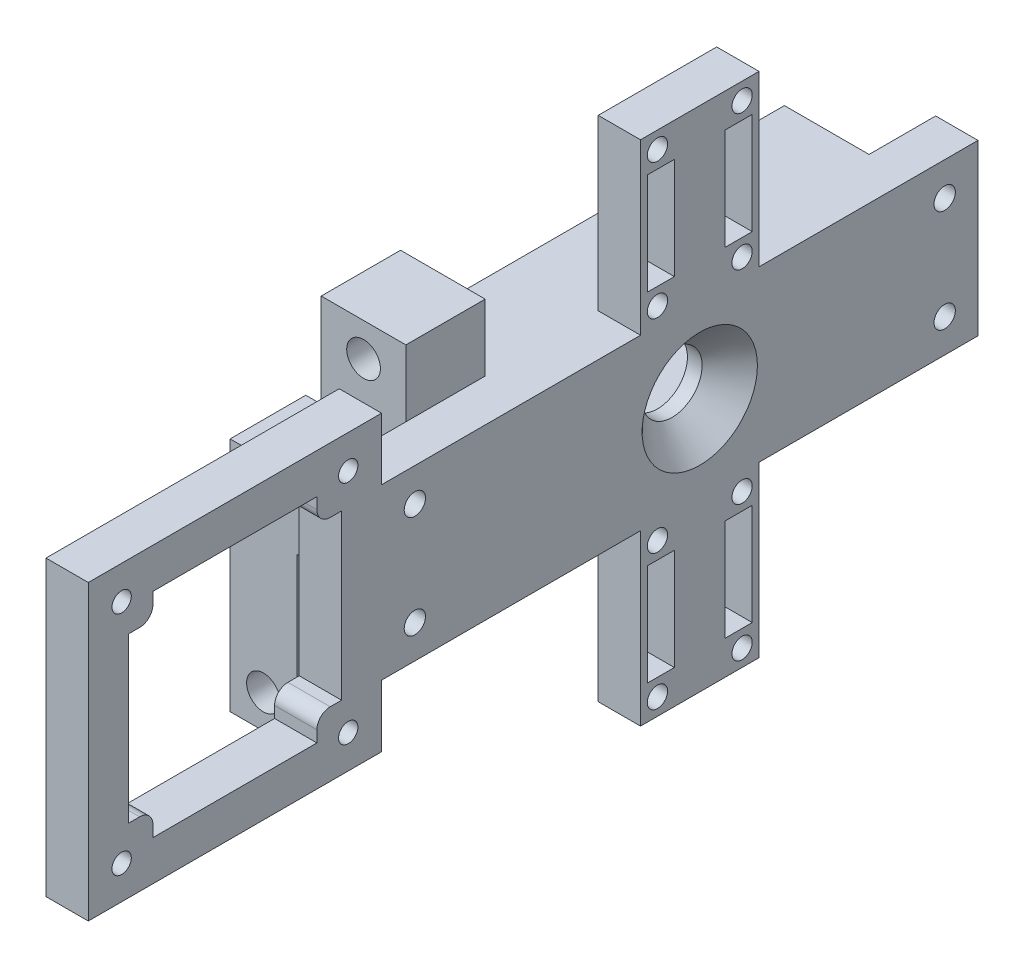
SolidWorks part; units mm, degrees
ref_plane "Front Plane" through (0, 0, 0) normal (0, 0, 1) x (1, 0, 0)
ref_plane "Top Plane" through (0, 0, 0) normal (0, 1, 0) x (1, 0, 0)
ref_plane "Right Plane" through (0, 0, 0) normal (1, 0, 0) x (0, 0, -1)
sketch "Sketch1" plane through (0, 0, 0) normal (0, 1, 0) x (1, 0, 0)
  line L1 (0, 0) -> (6.35, 0)
  line L2 (0, 0) -> (0, 89.5)
  line L3 (0, 89.5) -> (6.35, 89.5)
  line L4 (6.35, 0) -> (6.35, 89.5)
  dimension "D1" = 89.5
  dimension "D2" = 6.35
extrude "Boss-Extrude1" add sketch "Sketch1" along normal blind 25.4
sketch "Sketch2" plane through (0, 0, 0) normal (-1, 0, 0) x (0, 0, 1)
  line L0 (-89.5, 25.4) -> (0, 25.4) construction
  line L1 (-74.15, 20.05) -> (-21.35, 20.05)
  line L2 (-74.15, 20.05) -> (-74.15, 5.35)
  line L3 (-74.15, 5.35) -> (-21.35, 5.35)
  line L4 (-21.35, 20.05) -> (-21.35, 5.35)
  line L6 (-89.5, 25.4) -> (-89.5, 0) construction
  line L13 (-89.5, 0) -> (0, 0) construction
  line L14 (-79.5, 25.4) -> (-10, 25.4)
  line L15 (-79.5, 25.4) -> (-79.5, 0)
  line L16 (-79.5, 0) -> (-10, 0)
  line L17 (-10, 25.4) -> (-10, 0)
  line L18 (0, 25.4) -> (0, 0) construction
  dimension "D1" = 52.8
  dimension "D2" = 14.7
  dimension "D3" = 5.35
  dimension "D4" = 15.35
  dimension "D5" = 10
  dimension "D6" = 10
sketch "Sketch4" plane through (6.35, 0, 0) normal (1, 0, 0) x (0, 0, -1)
  line L0 (0, 25.4) -> (0, 0) construction
  line L1 (0, 34.7) -> (-44, 34.7)
  line L2 (0, 34.7) -> (0, -9.3)
  line L3 (0, -9.3) -> (-44, -9.3)
  line L4 (-44, 34.7) -> (-44, -9.3)
  line L6 (0, 25.4) -> (89.5, 25.4) construction
  circle A0 centre (-39, 29.7) radius 1.45
  circle A1 centre (-5, 29.7) radius 1.45
  circle A2 centre (-39, -4.3) radius 1.45
  circle A3 centre (-5, -4.3) radius 1.45
  dimension "D4" = 34
  dimension "D6" = 2.9
  dimension "D7" = 34
  dimension "D1" = 44
  dimension "D2" = 9.3
  dimension "D3" = 44
  dimension "D5" = 5
  dimension "D8" = 5
extrude "Boss-Extrude2" add sketch "Sketch4" against normal up to surface (6.35 mm away) up to face at (0, 12.7, -44.75)
hole_wizard "CSK for M8 Flat Head Machine Screw1" positions "Sketch6" profile "Sketch7" countersink size "M8" standard "ANSI Metric"
sketch "Sketch6" plane through (6.35, 0, 0) normal (1, 0, 0) x (0, 0, -1)
  line L1 (89.5, 25.4) -> (89.5, 0) construction
  line L2 (0, 25.4) -> (89.5, 25.4) construction
  point P0 (47.75, 12.7)
  dimension "D1" = 41.75
  dimension "D2" = 12.7
sketch "Sketch7" plane through (6.35, 12.7, -47.75) normal (0, 1, 0) x (0, 0, -1)
  line L0 (0, 0) -> (0, 20.2039)
  line L1 (0, 20.2039) -> (4.5, 17.5)
  line L2 (4.5, 17.5) -> (4.5, 4.15)
  line L3 (4.5, 4.15) -> (8.65, 0)
  line L5 (8.65, 0) -> (0, 0)
  line L6 (-4.5, 4.15) -> (-8.65, 0) construction
  line L10 (0, 20.2039) -> (-4.5, 17.5) construction
  line L11 (0, -6.35) -> (0, 107.95) construction
  dimension "Hole Dia." = 9
  dimension "Hole Depth" = 17.5
  dimension "Near C'Sink Dia." = 17.3
  dimension "Near C'Sink Angle" = 90
  dimension "Drill Angle" = 118
extrude "Boss-Extrude3" add sketch "Sketch2" along normal blind 12.7
sketch "Sketch9" plane through (0, 0, 0) normal (-1, 0, 0) x (0, 0, 1)
  line L1 (0, 34.7) -> (0, 25.4) construction
  line L2 (-10, 25.4) -> (0, 25.4) construction
  line L3 (-10, 0) -> (0, 0) construction
  line L4 (-89.5, 25.4) -> (-89.5, 0) construction
  circle A0 centre (-5, 20.4) radius 1.6
  circle A1 centre (-5, 5) radius 1.6
  circle A3 centre (-84.5, 5) radius 1.6
  circle A4 centre (-84.5, 20.4) radius 1.6
  dimension "D1" = 3.2
  dimension "D2" = 5
  dimension "D3" = 5
  dimension "D4" = 5
  dimension "D5" = 5
extrude "Cut-Extrude1" cut sketch "Sketch9" against normal up to surface (6.35 mm away) up to face at (6.35, 12.7, -56.4)
sketch "Sketch10" plane through (6.35, 0, 0) normal (1, 0, 0) x (0, 0, -1)
  line L0 (0, 25.4) -> (89.5, 25.4) construction
  line L1 (38.86, 25.4) -> (56.64, 25.4)
  line L2 (38.86, 25.4) -> (38.86, 50.8)
  line L3 (38.86, 50.8) -> (56.64, 50.8)
  line L4 (56.64, 25.4) -> (56.64, 50.8)
  line L5 (89.5, 25.4) -> (89.5, 0) construction
  line L7 (0, 0) -> (89.5, 0) construction
  line L8 (38.86, 0) -> (56.64, 0)
  line L9 (38.86, 0) -> (38.86, -25.4)
  line L10 (38.86, -25.4) -> (56.64, -25.4)
  line L11 (56.64, 0) -> (56.64, -25.4)
  circle A0 centre (41.4, 27.94) radius 1.524
  circle A1 centre (54.1, 27.94) radius 1.524
  circle A2 centre (54.1, 48.26) radius 1.524
  circle A3 centre (41.4, 48.26) radius 1.524
  circle A4 centre (41.4, -2.54) radius 1.524
  circle A5 centre (54.1, -2.54) radius 1.524
  circle A6 centre (41.4, -22.86) radius 1.524
  circle A7 centre (54.1, -22.86) radius 1.524
  point P25 (47.75, 50.8)
  dimension "D3" = 3.048
  dimension "D11" = 2.54
  dimension "D1" = 25.4
  dimension "D2" = 17.78
  dimension "D4" = 20.32
  dimension "D5" = 12.7
  dimension "D6" = 2.54
  dimension "D7" = 2.54
  dimension "D8" = 41.75
  dimension "D9" = 25.4
  dimension "D10" = 17.78
  dimension "D12" = 20.32
extrude "Boss-Extrude4" add sketch "Sketch10" against normal blind 6.35
sketch "Sketch11" plane through (6.35, 0, 0) normal (1, 0, 0) x (0, 0, -1)
  line L0 (0, 0) -> (38.86, 0) construction
  line L1 (39.876, -5.08) -> (43.94, -5.08)
  line L2 (39.876, -5.08) -> (39.876, -20.32)
  line L3 (39.876, -20.32) -> (43.94, -20.32)
  line L4 (43.94, -5.08) -> (43.94, -20.32)
  line L5 (51.56, -5.08) -> (55.624, -5.08)
  line L6 (51.56, -5.08) -> (51.56, -20.32)
  line L7 (51.56, -20.32) -> (55.624, -20.32)
  line L8 (55.624, -5.08) -> (55.624, -20.32)
  line L9 (38.86, -25.4) -> (56.64, -25.4) construction
  line L10 (38.86, 0) -> (38.86, -25.4) construction
  line L11 (56.64, -25.4) -> (56.64, 0) construction
  line L12 (56.64, 50.8) -> (38.86, 50.8) construction
  line L13 (39.876, 45.72) -> (43.94, 45.72)
  line L14 (39.876, 45.72) -> (39.876, 30.48)
  line L15 (39.876, 30.48) -> (43.94, 30.48)
  line L16 (43.94, 45.72) -> (43.94, 30.48)
  line L17 (51.56, 45.72) -> (55.624, 45.72)
  line L18 (51.56, 45.72) -> (51.56, 30.48)
  line L19 (51.56, 30.48) -> (55.624, 30.48)
  line L20 (55.624, 45.72) -> (55.624, 30.48)
  line L21 (0, 25.4) -> (38.86, 25.4) construction
  dimension "D1" = 5.08
  dimension "D2" = 5.08
  dimension "D3" = 1.016
  dimension "D4" = 4.064
  dimension "D5" = 1.016
  dimension "D6" = 5.08
  dimension "D7" = 5.08
extrude "Cut-Extrude2" cut sketch "Sketch11" against normal up to surface (6.35 mm away) up to face at (0, -22.86, -55.624)
sketch "Sketch14" plane through (0, 25.4, 0) normal (0, 1, 0) x (1, 0, 0)
  line L0 (-12.7, 10) -> (-12.7, 79.5) construction
  line L1 (0, 10) -> (-12.7, 10)
  line L2 (0, 10) -> (0, 21.9)
  line L3 (0, 21.9) -> (-12.7, 21.9)
  line L4 (-12.7, 10) -> (-12.7, 21.9)
  dimension "D1" = 11.9
extrude "Boss-Extrude5" add sketch "Sketch14" along normal blind 10
sketch "Sketch15" plane through (0, 0, -10) normal (0, 0, 1) x (1, 0, 0)
  line L0 (-12.7, 0) -> (-12.7, 35.4) construction
  line L1 (-12.7, 35.4) -> (0, 35.4) construction
  circle A0 centre (-6.35, 30.4) radius 2.5273
  dimension "D1" = 6.35
  dimension "D2" = 5.0546
  dimension "D3" = 5
extrude "Cut-Extrude4" cut sketch "Sketch15" against normal blind 7
sketch "Sketch16" plane through (-12.7, 0, 0) normal (-1, 0, 0) x (0, 0, 1)
  line L0 (-10, 0) -> (-10, 35.4) construction
  line L1 (-10, 10) -> (-21.35, 10)
  line L2 (-10, 10) -> (-10, 0)
  line L3 (-10, 0) -> (-21.35, 0)
  line L4 (-21.35, 10) -> (-21.35, 0)
  line L5 (-79.5, 0) -> (-10, 0) construction
  dimension "D1" = 10
  dimension "D2" = 11.35
extrude "Boss-Extrude6" add sketch "Sketch16" along normal blind 13.6718
sketch "Sketch17" plane through (0, 0, 0) normal (0, -1, 0) x (1, 0, 0)
  line L0 (-26.3718, -21.35) -> (-12.7, -21.35) construction
  line L1 (-26.3718, -10) -> (-16.3718, -10)
  line L2 (-26.3718, -10) -> (-26.3718, -21.35)
  line L3 (-26.3718, -21.35) -> (-16.3718, -21.35)
  line L4 (-16.3718, -10) -> (-16.3718, -21.35)
  dimension "D1" = 10
extrude "Boss-Extrude7" add sketch "Sketch17" along normal blind 25.4523
sketch "Sketch18" plane through (0, 0, -10) normal (0, 0, 1) x (1, 0, 0)
  line L0 (-16.3718, -25.4523) -> (-26.3718, -25.4523) construction
  line L1 (-26.3718, -25.4523) -> (-26.3718, 10) construction
  circle A0 centre (-21.3718, -20.4523) radius 2.5273
  circle A1 centre (-6.35, 30.4) radius 2.5273 construction
  dimension "D1" = 5
  dimension "D2" = 5
extrude "Cut-Extrude5" cut sketch "Sketch18" against normal blind 7
sketch "Sketch19" plane through (0, 0, 0) normal (0, -1, 0) x (1, 0, 0)
  line L0 (-12.7, -79.5) -> (-12.7, -21.35) construction
  line L1 (-12.7, -47.925) -> (-18.0384, -47.925)
  line L2 (-12.7, -47.925) -> (-12.7, -57.925)
  line L3 (-12.7, -57.925) -> (-18.0384, -57.925)
  line L4 (-18.0384, -47.925) -> (-18.0384, -57.925)
  line L5 (-16.3718, -21.35) -> (-12.7, -21.35) construction
  dimension "D1" = 10
  dimension "D2" = 26.575
  dimension "D3" = 5.3384
extrude "Boss-Extrude8" add sketch "Sketch19" against normal up to surface (5.35 mm away) up to face at (-6.35, 5.35, -47.75)
sketch "Sketch21" plane through (0, 0, 0) normal (0, -1, 0) x (1, 0, 0)
  line L1 (-24.32, -39.85) -> (-14.32, -39.85)
  line L2 (-24.32, -39.85) -> (-24.32, -49.85)
  line L3 (-24.32, -49.85) -> (-14.32, -49.85)
  line L4 (-14.32, -39.85) -> (-14.32, -49.85)
  line L5 (-16.9785, -23.35) -> (-8.8616, -23.35)
  line L6 (-16.9785, -23.35) -> (-16.9785, -28.35)
  line L7 (-16.9785, -28.35) -> (-8.8616, -28.35)
  line L8 (-8.8616, -23.35) -> (-8.8616, -28.35)
  line L10 (-16.9785, -61.35) -> (-8.8616, -61.35)
  line L11 (-16.9785, -61.35) -> (-16.9785, -66.35)
  line L12 (-16.9785, -66.35) -> (-8.8616, -66.35)
  line L13 (-8.8616, -61.35) -> (-8.8616, -66.35)
  line L17 (-16.3718, -21.35) -> (-12.7, -21.35) construction
  line L18 (-12.7, -47.925) -> (-12.7, -21.35) construction
  point P12 (-14.32, -44.85)
  point P19 (-19.32, -39.85)
  dimension "D1" = 21.5
  dimension "D2" = 10.4584
  dimension "D3" = 5
  dimension "D4" = 43
  dimension "D5" = 5
  dimension "D6" = 10
  dimension "D7" = 8.1169
  dimension "D8" = 10
  dimension "D9" = 2
  dimension "D10" = 3.8384
extrude "Boss-Extrude9" add sketch "Sketch21" along normal blind 11.85
sketch "Sketch22" plane through (0, -11.85, 0) normal (0, -1, 0) x (1, 0, 0)
  line L2 (-14.32, -49.85) -> (-14.32, -39.85) construction
  line L3 (-24.32, -49.85) -> (-14.32, -49.85) construction
  circle A1 centre (-19.32, -44.85) radius 2.5273
  dimension "D1" = 5.0546
  dimension "D3" = 5
  dimension "D2" = 5
extrude "Cut-Extrude6" cut sketch "Sketch22" against normal blind 7
sketch "Sketch25" plane through (-18.0384, 0, 0) normal (-1, 0, 0) x (0, 0, 1)
  line L5 (-47.925, 5.35) -> (-47.925, 0) construction
  line L6 (-57.925, 5.35) -> (-47.925, 5.35)
  line L7 (-57.925, 5.35) -> (-57.925, 0)
  line L8 (-57.925, 0) -> (-47.925, 0)
  line L9 (-47.925, 5.35) -> (-47.925, 0)
  line L10 (-56.64, 0) -> (-38.86, 0) construction
extrude "Cut-Extrude7" cut sketch "Sketch25" against normal up to surface (5.3384 mm away) up to face at (-12.7, 1.7833, -31.7083)
sketch "Sketch26" plane through (6.35, 0, 0) normal (1, 0, 0) x (0, 0, -1)
  line L23 (-34.3, 28.7) -> (-9.7, 28.7)
  line L26 (-38, 25) -> (-38, 0.4)
  line L27 (-34.3, -3.3) -> (-9.7, -3.3)
  line L28 (-6, 25) -> (-6, 0.4)
  line L30 (-44, 34.7) -> (-44, -9.3) construction
  line L31 (-44, -9.3) -> (0, -9.3) construction
  line L33 (-34.3, 28.7) -> (-34.3, 25)
  line L34 (-38, 25) -> (-34.3, 25)
  line L35 (-9.7, 28.7) -> (-9.7, 25)
  line L36 (-9.7, 25) -> (-6, 25)
  line L37 (-6, 0.4) -> (-9.7, 0.4)
  line L38 (-9.7, 0.4) -> (-9.7, -3.3)
  line L39 (-38, 0.4) -> (-34.3, 0.4)
  line L40 (-34.3, 0.4) -> (-34.3, -3.3)
  line L41 (0, 25.4) -> (0, 34.7) construction
  line L42 (0, 34.7) -> (-44, 34.7) construction
  dimension "D5" = 3.7
  dimension "D6" = 3.7
  dimension "D9" = 3.7
  dimension "D11" = 3.7
  dimension "D7" = 6
  dimension "D2" = 3.7
  dimension "D3" = 6
  dimension "D4" = 6
  dimension "D8" = 3.7
  dimension "D10" = 3.7
  dimension "D12" = 6
extrude "Cut-Extrude8" cut sketch "Sketch26" against normal up to surface (6.35 mm away) up to face at (0, 5, -3.4)
fillet "Fillet1" radius 2 4 edges at (3.175, 25, 9.7) (3.175, 0.4, 34.3) (3.175, 0.4, 9.7) (3.175, 25, 34.3)
sketch "Sketch27" plane through (-14.32, 0, 0) normal (1, 0, 0) x (0, 0, -1)
  line L1 (39.85, 0) -> (49.85, 0)
  line L2 (39.85, 0) -> (39.85, -11.85)
  line L3 (39.85, -11.85) -> (49.85, -11.85)
  line L4 (49.85, 0) -> (49.85, -11.85)
extrude "Boss-Extrude10" add sketch "Sketch27" along normal blind 5
equation "\"D1@Cut-Extrude4\"=4"
